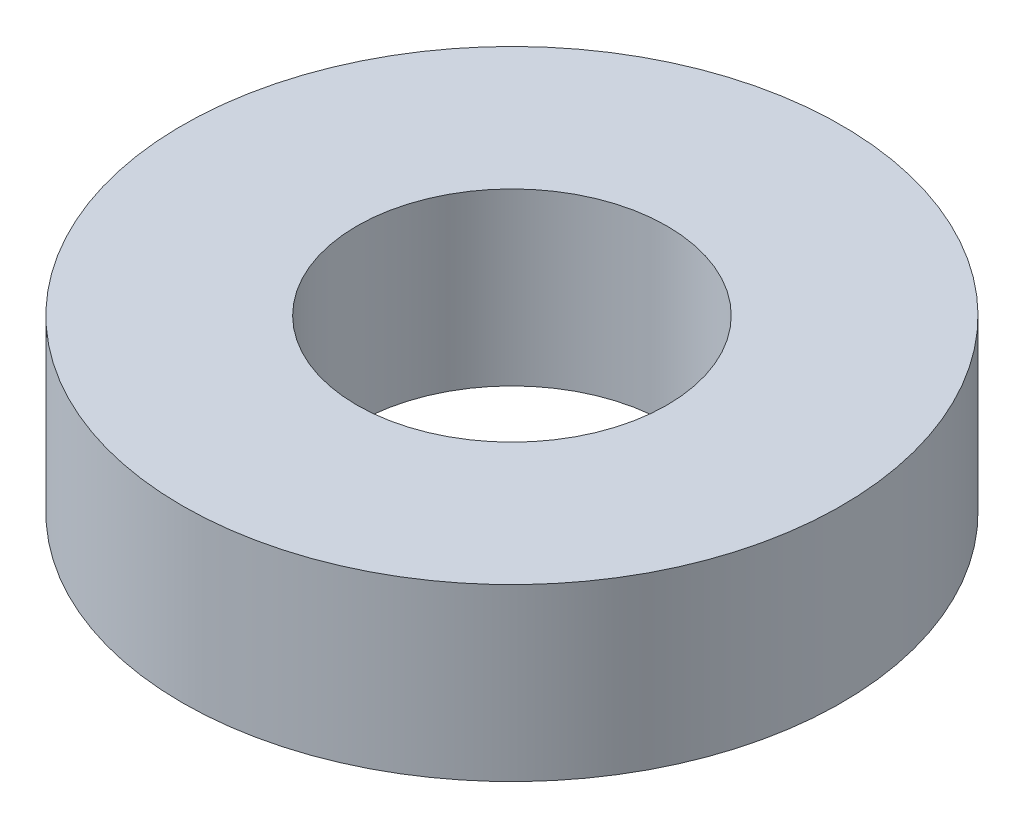
SolidWorks part; units mm, degrees
ref_plane "Front Plane" through (0, 0, 0) normal (0, 0, 1) x (1, 0, 0)
ref_plane "Top Plane" through (0, 0, 0) normal (0, 1, 0) x (1, 0, 0)
ref_plane "Right Plane" through (0, 0, 0) normal (1, 0, 0) x (0, 0, -1)
sketch "Sketch1" plane through (0, 0, 0) normal (0, 1, 0) x (1, 0, 0)
  circle A0 centre (0, 0) radius 42.5
  dimension "FLANGE_OD" = 85
extrude "Boss-Extrude1" add sketch "Sketch1" along normal blind 22
sketch "Sketch2" plane through (0, 0, 0) normal (0, 1, 0) x (1, 0, 0)
  circle A0 centre (0, 0) radius 20
  dimension "BORE_D" = 40
extrude "Cut-Extrude1" cut sketch "Sketch2" along normal through all
sketch "Sketch3" plane through (0, 22, 0) normal (0, 1, 0) x (1, 0, 0)
  circle A0 centre (0, 0) radius 14.5864 construction
  circle A1 centre (-14.5864, 0) radius 2.5377
  dimension "BOLT_D" = 5.0754
  dimension "BOLT_PCD" = 29.1727
extrude "Cut-Extrude2" cut sketch "Sketch3" against normal blind 20.4757 rebuild error yes
pattern_circular "CirPattern1" count 3 over 360 rebuild error yes
